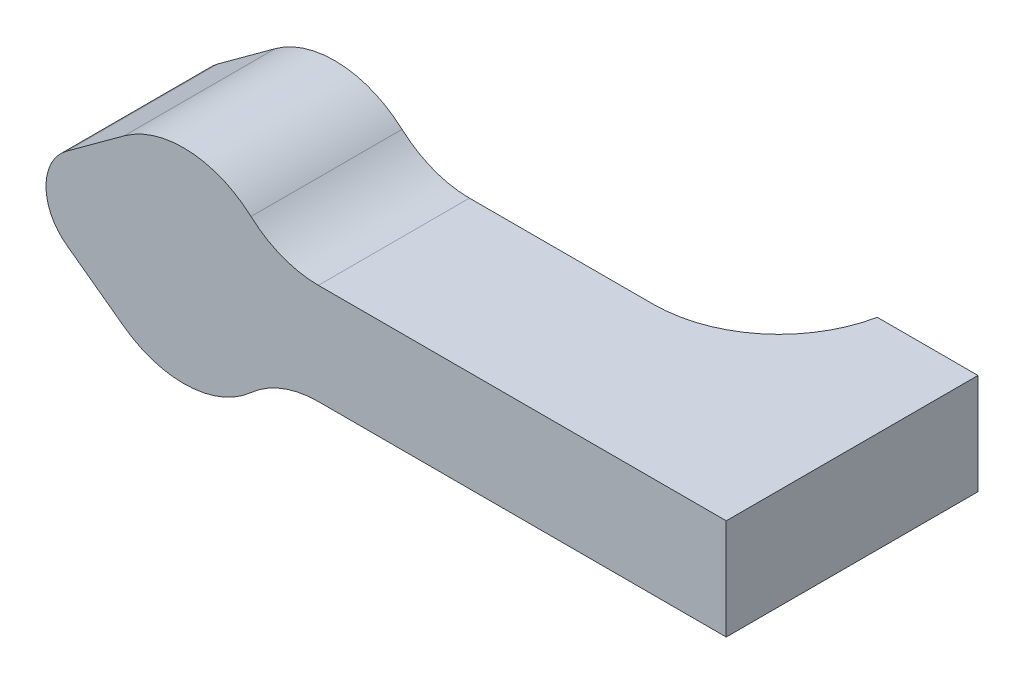
SolidWorks part; units mm, degrees
material "6061-T6 (SS)"
ref_plane "Front Plane" through (0, 0, 0) normal (0, 0, 1) x (1, 0, 0)
ref_plane "Top Plane" through (0, 0, 0) normal (0, 1, 0) x (1, 0, 0)
ref_plane "Right Plane" through (0, 0, 0) normal (1, 0, 0) x (0, 0, -1)
sketch "Sketch1" plane through (0, 0, 0) normal (0, 0, 1) x (1, 0, 0)
  line L0 (-3.05, 3) -> (-6.05, 0.8073)
  line L5 (-4.939, -1.6193) -> (-3.05, -1) construction
  line L6 (-4.939, 1.6193) -> (-3.05, 1) construction
  line L7 (-6.05, 0.8073) -> (-4.4045, -1.4441) construction
  line L8 (-6.05, -0.8073) -> (-3.05, -3)
  line L9 (-6.05, -0.8073) -> (-4.4045, 1.4441) construction
  line L10 (7.05, 1) -> (7.05, -1)
  line L15 (-3.05, 1) -> (-3.05, 3)
  line L16 (3.05, -1) -> (-3.05, -1)
  line L17 (-3.05, -1) -> (-3.05, -3)
  line L19 (3.05, 1) -> (-3.05, 1)
  line L21 (3.05, -1) -> (-3.05, 1) construction
  line L22 (3.05, 1) -> (-3.05, -1) construction
  line L23 (3.05, 1) -> (7.05, 1)
  line L25 (3.05, -1) -> (7.05, -1)
  arc A0 (-6.05, 0.8073) -> (-6.05, -0.8073) centre (-5.4599, 0) ccw
  point P0 (0, 0)
  point P1 (0, 0)
  dimension "D6" = 4
  dimension "D4" = 1
  dimension "D1" = 6.1
  dimension "D2" = 2
  dimension "D3" = 3
  dimension "D5" = 2
  dimension "D7" = 6.1
extrude "Boss-Extrude1" add sketch "Sketch1" along normal blind 3 contours L8 L0 region at (-0.3479, 0, 0)
fillet "Fillet2" radius 2 2 edges at (-3.05, -1, 1.5) (-3.05, 1, 1.5)
fillet "Fillet3" radius 2 2 edges at (-3.05, -3, 1.5) (-3.05, 3, 1.5)
sketch "Sketch3" plane through (0, 1, 0) normal (0, 1, 0) x (1, 0, 0)
  line L0 (-1.05, -3) -> (7.05, -3) construction
  line L1 (5.05, -3) -> (7.05, -3)
  line L2 (5.05, -3) -> (5.05, 2)
  line L3 (5.05, 2) -> (7.05, 2)
  line L4 (7.05, -3) -> (7.05, 2)
  line L6 (7.05, -3) -> (7.05, 0) construction
  point P7 (6.05, -3)
  point P8 (7.05, 5.8875)
  dimension "D2" = 5
  dimension "D3" = 2
extrude "Boss-Extrude3" add sketch "Sketch3" against normal up to surface (2 mm away) up to face at (3, -1, 1.5)
fillet "Fillet5" radius 2.5 1 edges at (5.05, 0, 0)
